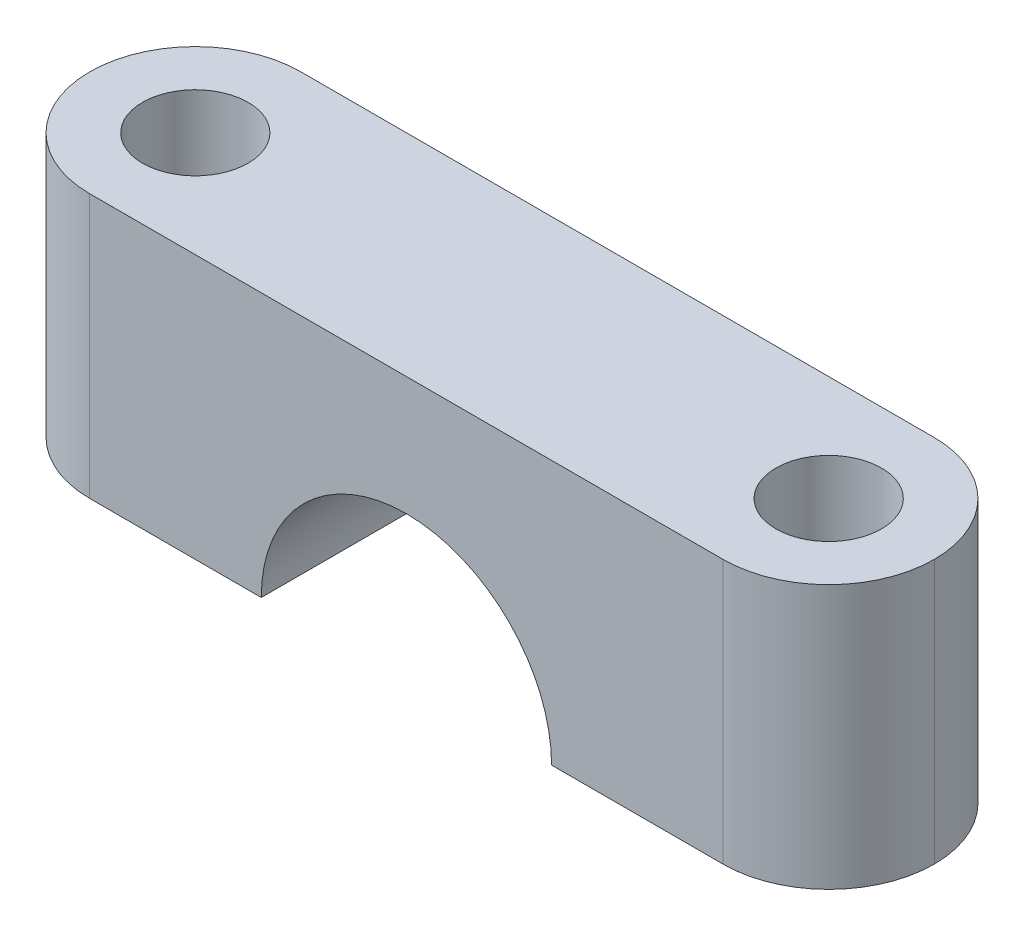
SolidWorks part; units mm, degrees
material "6061-T6 (SS)"
ref_plane "Front Plane" through (0, 0, 0) normal (0, 0, 1) x (1, 0, 0)
ref_plane "Top Plane" through (0, 0, 0) normal (0, 1, 0) x (1, 0, 0)
ref_plane "Right Plane" through (0, 0, 0) normal (1, 0, 0) x (0, 0, -1)
sketch "Sketch1" plane through (0, 0, 0) normal (0, 0, 1) x (1, 0, 0)
  line L0 (-8.7312, 0) -> (-25.4, 0)
  line L1 (-25.4, 0) -> (-25.4, 15.875)
  line L2 (-25.4, 15.875) -> (25.4, 15.875)
  line L3 (25.4, 15.875) -> (25.4, 0)
  line L4 (25.4, 0) -> (8.7312, 0)
  line L5 (0, 0) -> (0, 15.875) construction
  arc A0 (8.7312, 0) -> (-8.7312, 0) centre (0, 0) ccw
  dimension "D1" = 8.7312
  dimension "D2" = 50.8
  dimension "D3" = 15.875
extrude "Boss-Extrude1" add sketch "Sketch1" along normal mid plane 12.7
sketch "Sketch2" plane through (0, 0, 0) normal (0, 1, 0) x (1, 0, 0)
  line L0 (19.05, 0) -> (-19.05, 0) construction
  circle A0 centre (-19.05, 0) radius 3.175
  circle A1 centre (19.05, 0) radius 3.175
  point P4 (0, 0)
  dimension "D2" = 6.35
  dimension "D1" = 38.1
extrude "Cut-Extrude1" cut sketch "Sketch2" along normal through all
fillet "Fillet1" radius 6.35 4 edges at (25.4, 7.9375, -6.35) (25.4, 7.9375, 6.35) (-25.4, 7.9375, -6.35) (-25.4, 7.9375, 6.35)
